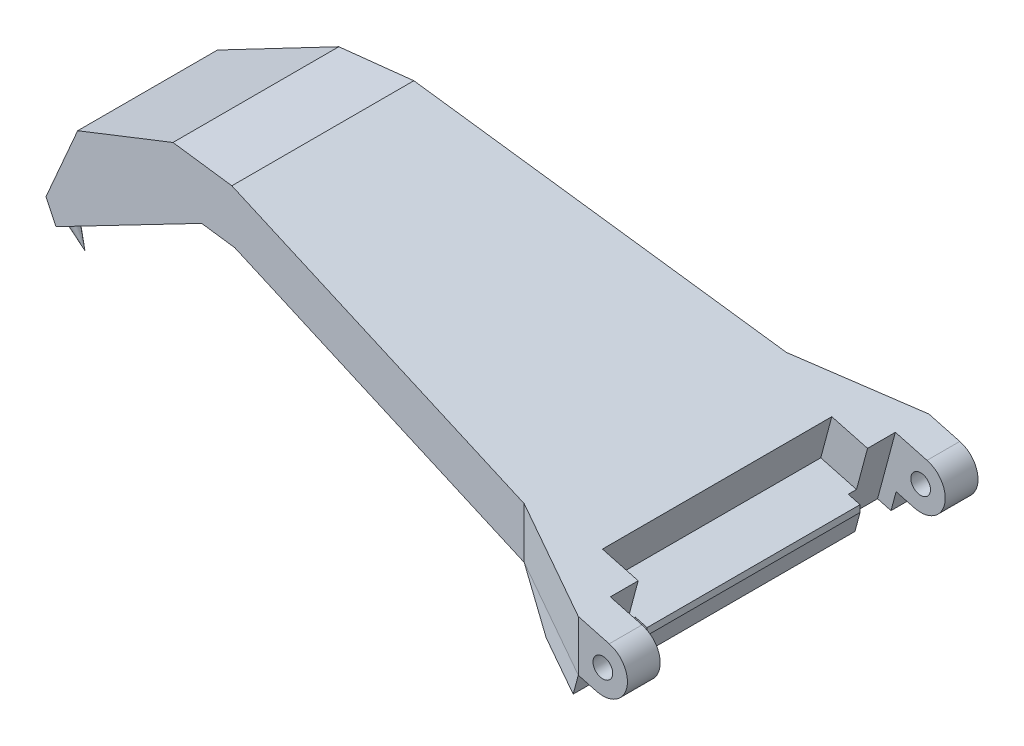
SolidWorks part; units mm, degrees
material "ABS"
ref_plane "Front Plane" through (0, 0, 0) normal (0, 0, 1) x (1, 0, 0)
ref_plane "Top Plane" through (0, 0, 0) normal (0, 1, 0) x (1, 0, 0)
ref_plane "Right Plane" through (0, 0, 0) normal (1, 0, 0) x (0, 0, -1)
sketch "Sketch3" plane through (0, 0, 0) normal (0, 0, 1) x (1, 0, 0)
  line L0 (0.9706, 3.6222) -> (-69.4823, 22.5)
  line L1 (-69.4823, 22.5) -> (-79.7011, 22.5)
  line L2 (-79.7011, 22.5) -> (-96.234, 14.7906)
  line L3 (-96.234, 14.7906) -> (-101.7321, 3)
  line L4 (-101.7321, 3) -> (-100, 0)
  line L5 (-100, 0) -> (-74.715, 14.5983)
  line L6 (-74.715, 14.5983) -> (-68.9706, 14.5983)
  line L7 (-68.9706, 14.5983) -> (-0.9706, -3.6222)
  line L8 (-0.9706, -3.6222) -> (0.9706, 3.6222) construction
  line L9 (-5.6356, -2.3722) -> (-3.6945, 4.8722) construction
  line L10 (-100, 0) -> (0, 0) construction
  circle A0 centre (0, 0) radius 1.5
  arc A2 (-0.9706, -3.6222) -> (0.9706, 3.6222) centre (0, 0) ccw
  point P14 (-5, 0)
  dimension "D2" = 3
  dimension "D1" = 100
  dimension "D3" = 7.5
  dimension "D4" = 68
  dimension "D5" = 30
  dimension "D6" = 15
  dimension "D7" = 125
  dimension "D8" = 5.498
  dimension "D9" = 3
  dimension "D10" = 155
  dimension "D11" = 22.5
sketch "start-width" plane through (0, 0, 0) normal (1, 0, 0) x (0, 0, -1)
  line L0 (-26.75, 0) -> (26.75, 0)
  point P4 (0, 0)
  dimension "D1" = 53.5
ref_plane "Plane1" through (-101.7321, 0, 0) normal (1, 0, 0) x (0, 0, -1)
sketch "end-width" plane through (-101.7321, 0, 0) normal (1, 0, 0) x (0, 0, -1)
  line L0 (10, 0) -> (-10, 0)
  point P4 (0, 0)
  dimension "D1" = 20
sketch "picture-background" plane through (0, 0, 0) normal (0, 0, 1) x (1, 0, 0)
  line L0 (-153.9208, -162.5929) -> (-22.7793, -162.5929) construction
extrude "Boss-Extrude2" add sketch "Sketch3" along direction (0, 0, -1) on the side against the normal up to vertex (26.75 mm away) and the other way up to vertex (26.75 mm away) up to point (0, 0, -26.75) other way up to point (0, 0, 26.75)
sketch "Sketch12" plane through (0, 0, 0) normal (0, 1, 0) x (1, 0, 0)
  line L0 (-101.7321, 10) -> (-101.7321, -10) construction
  line L1 (-101.7321, 10) -> (-3.75, 10) construction
  line L2 (-101.7321, 10) -> (-101.7321, -10)
  line L3 (-3.75, -26.75) -> (-3.75, 26.75)
  line L4 (-101.7321, 10) -> (-3.75, 26.75) construction
  line L5 (-101.7321, -10) -> (-3.75, -26.75) construction
  line L6 (-101.7321, 0) -> (0, 0) construction
  line L7 (0, -26.75) -> (0, 26.75) construction
  line L8 (0, -26.75) -> (0, 26.75) construction
  line L9 (-101.7321, 10) -> (-18.75, 20)
  line L10 (-18.75, 20) -> (-3.75, 26.75)
  line L11 (-18.75, -20) -> (-3.75, -26.75)
  line L12 (-101.7321, -10) -> (-18.75, -20)
  dimension "D1" = 3.75
  dimension "D2" = 20
  dimension "D3" = 15
extrude "top-form" cut sketch "Sketch12" along normal through all and the other way through all flip side to cut contours L2 L12 L11 L3 L10 L9 | L3 L10 L9 L2 L12 L11 region at (-45.7976, 0, 0)
sketch "Sketch13" plane through (0, 0, 0) normal (0, 0, 1) x (1, 0, 0)
  line L0 (-3.75, 4.8871) -> (-3.75, -2.8775) construction
  line L1 (-3.75, 4.8871) -> (-3.75, -2.8775)
  line L8 (0.9706, 3.6222) -> (-3.75, 4.8871)
  line L9 (-0.9706, -3.6222) -> (-3.75, -2.8775)
  arc A0 (-0.9706, -3.6222) -> (0.9706, 3.6222) centre (0, 0) ccw construction
  circle A1 centre (0, 0) radius 1.5 construction
  arc A2 (-0.9706, -3.6222) -> (0.9706, 3.6222) centre (0, 0) ccw
  circle A3 centre (0, 0) radius 1.5
extrude "end-extrude" add sketch "Sketch13" along direction (0, 0, 1) on the side of the normal up to vertex (26.75 mm away) and the other way up to vertex (26.75 mm away) up to point (-3.75, 4.8871, 26.75) other way up to point (-3.75, 4.8871, -26.75)
sketch "Sketch16" plane through (0.9706, 3.6222, 0) normal (0.2588, 0.9659, 0) x (0.9659, -0.2588, 0)
  line L0 (3.75, -26.75) -> (3.75, 26.75) construction
  line L1 (3.75, -26.75) -> (3.75, 26.75) construction
  line L2 (3.75, 26.75) -> (0, 26.75) construction
  line L3 (0, -26.75) -> (3.75, -26.75) construction
  line L4 (3.75, 26.75) -> (0, 26.75) construction
  line L5 (0, -26.75) -> (3.75, -26.75) construction
  line L6 (0, 26.75) -> (-4.8871, 26.75) construction
  line L7 (0, -26.75) -> (-4.8871, -26.75) construction
  line L8 (0, 26.75) -> (-4.8871, 26.75) construction
  line L9 (0, -26.75) -> (-4.8871, -26.75) construction
  line L10 (-4.8871, -26.75) -> (-4.8871, 26.75) construction
  line L11 (3.75, 0) -> (-4.8871, 0) construction
  line L14 (-4.8871, -21.75) -> (3.75, -21.75)
  line L15 (-4.8871, 21.75) -> (3.75, 21.75)
  line L16 (3.75, -21.75) -> (-4.8871, -21.75)
  line L17 (-4.8871, -21.75) -> (-4.8871, 0)
  line L18 (3.75, 0) -> (3.75, -21.75)
  line L19 (-4.8871, 21.75) -> (-4.8871, 0)
  line L20 (3.75, 0) -> (3.75, 21.75)
  line L21 (3.75, 0) -> (3.75, -21.75)
  line L22 (-4.8871, -21.75) -> (-4.8871, 0)
  line M12 (0, -26.75) -> (0, 26.75)
  dimension "D1" = 43.5
extrude "spring_phalanx_place" cut sketch "Sketch16" along direction (0, -1, 0) on the side against the normal up to surface (7.5 mm away) contours L15 L19 L17 L14 M12 | L18 L20 L15 L14 M12 region at (-1.3897, 4.2547, 0) region at (2.7817, 3.1369, 0) up to face at (-23.1103, 2.3101, 0)
sketch "Sketch17" plane through (-25, 43.3013, 0) normal (0.5, -0.866, 0) x (0.866, 0.5, 0)
  line L0 (-86.6025, 0) -> (-57.4059, 0) construction
  line L1 (-86.6025, -10.2087) -> (-86.6025, 10.2087) construction
  line L2 (-57.4059, -13.2558) -> (-57.4059, 13.2558) construction
  line L3 (-86.6025, 10.2087) -> (-57.4059, 13.2558) construction
  circle A0 centre (-85.1025, 8.8571) radius 0.75
  circle A1 centre (-85.1025, -8.8571) radius 0.75
  dimension "D1" = 1.5
  dimension "D2" = 1.5
  dimension "D3" = 1.5
extrude "spikes" add sketch "Sketch17" along normal blind 6 draft 12
sketch "Sketch18" plane through (-0.9706, -3.6222, 0) normal (-0.2588, -0.9659, 0) x (0.9659, -0.2588, 0)
  line L0 (-18.4066, -20) -> (-2.8775, -26.75) construction
  line L2 (-18.4066, 20) -> (-2.8775, 26.75) construction
  line L4 (-2.8775, 26.75) -> (-2.8775, -26.75)
  line L5 (-18.4066, -20) -> (-18.4066, 20)
  line L7 (-18.4066, 20) -> (-2.8775, 26.75)
  line L8 (-18.4066, -20) -> (-2.8775, -26.75)
  line L9 (-2.8775, 26.75) -> (0, 26.75) construction
  line L10 (0, 26.75) -> (0, -26.75) construction
  line L11 (0, -26.75) -> (-2.8775, -26.75)
  line M4 (-2.8775, 26.75) -> (-18.4066, 20)
  line M8 (-18.4066, -20) -> (-2.8775, -26.75)
  line M12 (-2.8775, -21.75) -> (-2.8775, 21.75)
extrude "spring-support" add sketch "Sketch18" along normal blind 3 contours L5 L4 M8 M12 M4 region at (-10.889, -0.9646, 0)
ref_plane "spring-cut-out-plane" through (-0.7118, -2.6563, 0) normal (0.2588, 0.9659, 0) x (0.9659, -0.2588, 0)
sketch "Sketch21" plane through (-0.7118, -2.6563, 0) normal (0.2588, 0.9659, 0) x (0.9659, -0.2588, 0)
  line L0 (-4.8871, 21.75) -> (0, 21.75) construction
  line L1 (-4.8871, 21.75) -> (0, 21.75)
  line L2 (0, 0) -> (-11, 0) construction
  line L3 (-4.8871, -21.75) -> (0, -21.75) construction
  line L4 (-4.8871, -21.75) -> (-5, -21.75)
  line L5 (-4.8871, -21.75) -> (0, -21.75)
  line L6 (0, 16.25) -> (-5, 16.25)
  line L8 (-5, -21.75) -> (-5, -16.25)
  line L12 (0, -16.25) -> (0, -21.75)
  line L13 (0, 16.25) -> (0, 21.75)
  line L16 (-4.8871, 21.75) -> (-5, 21.75)
  line L17 (-5, 21.75) -> (-5, 16.25)
  line L19 (0, -16.25) -> (-5, -16.25)
  dimension "D1" = 5.5
  dimension "D3" = 5
sketch "Sketch22" plane through (0, 0, 0) normal (0, 0, 1) x (1, 0, 0)
  line L0 (-19.5265, -1.756) -> (-18.75, 1.1418) construction
  line L1 (-19.5265, -1.756) -> (-18.75, 1.1418)
  line L2 (-3.75, 4.8871) -> (-3.75, -2.8775) construction
  line L3 (-19.5265, -1.756) -> (-4.5265, -5.7753) construction
  line L4 (-18.75, 1.1418) -> (-12.0265, -3.7656)
  line L5 (-12.0265, -3.7656) -> (-19.5265, -1.756)
  line L6 (-19.5265, -1.756) -> (-4.5265, -5.7753) construction
  line L7 (-18.75, 1.1418) -> (-3.75, -2.8775) construction
  line L8 (-3.75, -1.8422) -> (-10.9944, 0.0989)
  line L9 (-10.9944, 0.0989) -> (-8.4063, 9.7582)
  line L12 (-3.75, 4.8871) -> (-3.75, -2.8775) construction
  line L13 (-3.75, 8.5106) -> (-3.75, -1.8422)
  line L14 (-18.75, 1.1418) -> (-3.75, -2.8775) construction
  line L15 (-3.75, 8.5106) -> (-3.75, -2.8775) construction
  line L16 (-8.4063, 9.7582) -> (-3.75, 8.5106)
  dimension "D1" = 7.5
  dimension "D2" = 1
  dimension "D3" = 10
extrude "spring-support-corner-cut" cut sketch "Sketch22" against normal through all both and the other way through all contours L4 L5 L1
extrude "spring-place-cut" cut sketch "Sketch22<3>" along normal blind 17.5 and the other way blind 17.5 contours L13 L8 L9 L16
sketch "Sketch22<3>" plane through (0, 0, 0) normal (0, 0, 1) x (1, 0, 0) same geometry as "Sketch22"
extrude "phalanx-space-cut" cut sketch "Sketch21" against normal through all both and the other way through all
